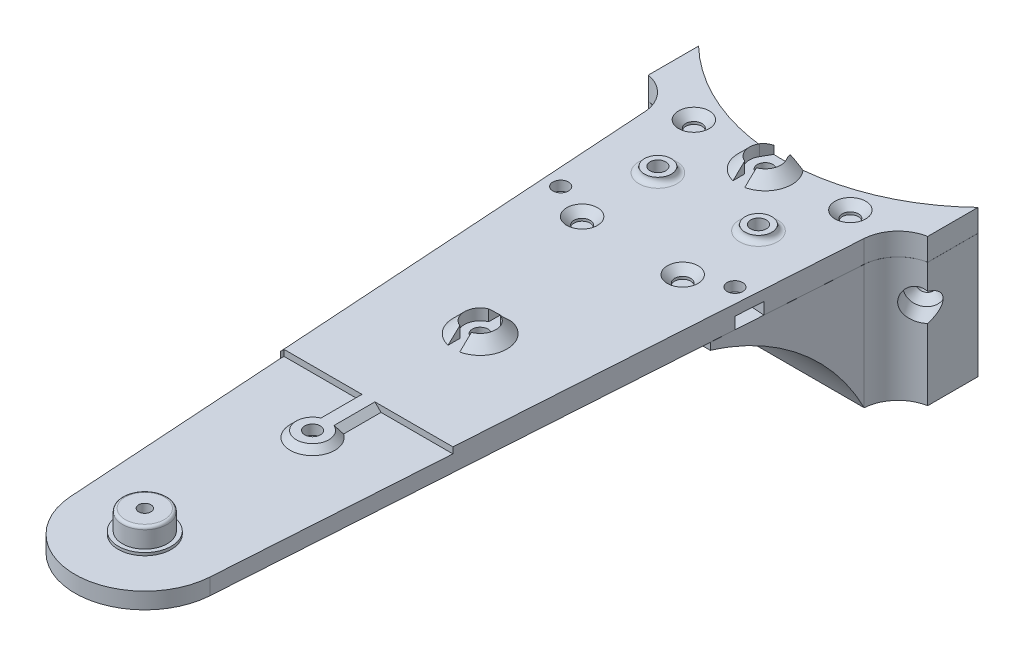
SolidWorks part; units mm, degrees
ref_plane "Front Plane" through (0, 0, 0) normal (0, 0, 1) x (1, 0, 0)
ref_plane "Top Plane" through (0, 0, 0) normal (0, 1, 0) x (1, 0, 0)
ref_plane "Right Plane" through (0, 0, 0) normal (1, 0, 0) x (0, 0, -1)
sketch "Sketch1" plane through (0, 0, 0) normal (0, 1, 0) x (1, 0, 0)
  line L0 (0, 0) -> (0, -150) construction
  line L1 (-22.2029, -1.4463) -> (-12.4736, -150.8125) construction
  line L2 (22.2029, -1.4462) -> (12.4736, -150.8125) construction
  line L3 (-12.4736, -150.8125) -> (-19.6328, -40.9037)
  line L4 (12.4736, -150.8125) -> (19.6328, -40.9037)
  line L5 (-25, -25.9037) -> (25, -25.9037) construction
  line L6 (-25, -25.9037) -> (-25, -34.9037)
  line L7 (25, -25.9037) -> (25, -34.9037)
  circle A0 centre (0, 0) radius 36 construction
  arc A1 (-12.4736, -150.8125) -> (12.4736, -150.8125) centre (0, -150) ccw
  circle A2 centre (0, 0) radius 19.5 construction
  circle A3 centre (0, 19.5) radius 2.75 construction
  circle A4 centre (0, 0) radius 22.25 construction
  arc A5 (-25, -25.9037) -> (25, -25.9037) centre (0, 0) ccw
  arc A6 (-25, -34.9037) -> (-19.6328, -40.9037) centre (-26.1442, -41.3278) cw
  arc A7 (25, -34.9037) -> (19.6328, -40.9037) centre (26.1442, -41.3278) ccw
  dimension "D1" = 72
  dimension "D3" = 25
  dimension "D4" = 39
  dimension "D5" = 5.5
  dimension "D2" = 150
  dimension "D6" = 50
  dimension "D7" = 9
  dimension "D8" = 15
extrude "Boss-Extrude1" add sketch "Sketch1" against normal blind 4
sketch "Sketch2" plane through (0, -4, 0) normal (0, -1, 0) x (1, 0, 0)
  line L0 (25, 34.9037) -> (25, 25.9037) construction
  line L1 (-25, 25.9037) -> (-25, 34.9037) construction
  line L2 (25, 34.9037) -> (25, 25.9037)
  line L3 (-25, 25.9037) -> (-25, 34.9037)
  line L4 (-19.6328, 40.9037) -> (19.6328, 40.9037)
  arc A0 (19.6328, 40.9037) -> (25, 34.9037) centre (26.1442, 41.3278) ccw construction
  arc A1 (25, 25.9037) -> (-25, 25.9037) centre (0, 0) ccw construction
  arc A2 (-25, 34.9037) -> (-19.6328, 40.9037) centre (-26.1442, 41.3278) ccw construction
  arc A3 (19.6328, 40.9037) -> (25, 34.9037) centre (26.1442, 41.3278) ccw
  arc A4 (25, 25.9037) -> (-25, 25.9037) centre (0, 0) ccw
  arc A5 (-25, 34.9037) -> (-19.6328, 40.9037) centre (-26.1442, 41.3278) ccw
extrude "Boss-Extrude2" add sketch "Sketch2" along normal offset from surface (22.2378 mm away) 26.2378 up to face at (0, 0, 65.6223)
ref_plane "Plane1" through (0, 0, 34.9037) normal (0, 0, 1) x (1, 0, 0)
fillet "Fillet2" radius 40 1 edges at (0, -4, 40.9037)
sketch "Sketch3" plane through (0, 0, 34.9037) normal (0, 0, 1) x (1, 0, 0)
  line L0 (25, 0) -> (-25, 0) construction
  line L1 (-19.6636, -22.6878) -> (19.6636, -22.6878) construction
  line L2 (-19.6636, -22.6878) -> (-19.6636, -10.6878) construction
  line L3 (-19.6636, -10.6878) -> (19.6636, -10.6878) construction
  line L4 (19.6636, -22.6878) -> (19.6636, -10.6878) construction
  line L5 (-19.6636, -22.6878) -> (19.6636, -10.6878) construction
  line L6 (-19.6636, -10.6878) -> (19.6636, -22.6878) construction
  line L7 (-19.6636, -7.9378) -> (-25, -7.9378)
  line L8 (-25, -7.9378) -> (-25, -13.4378)
  line L9 (-25, -13.4378) -> (-19.6636, -13.4378)
  line L10 (-25, -26.2378) -> (-25, 0) construction
  line L11 (0, -16.6878) -> (-25, -16.6878) construction
  line L12 (-25, -25.4378) -> (-25, -19.9378)
  line L13 (-25, -19.9378) -> (-19.6636, -19.9378)
  line L14 (-19.6636, -25.4378) -> (-25, -25.4378)
  line L15 (0, -16.6878) -> (0, 0) construction
  line L16 (19.6636, -25.4378) -> (25, -25.4378)
  line L17 (25, -19.9378) -> (19.6636, -19.9378)
  line L18 (25, -25.4378) -> (25, -19.9378)
  line L19 (25, -13.4378) -> (19.6636, -13.4378)
  line L20 (25, -7.9378) -> (25, -13.4378)
  line L21 (19.6636, -7.9378) -> (25, -7.9378)
  arc A0 (-19.6636, -13.4378) -> (-19.6636, -7.9378) centre (-19.6636, -10.6878) ccw
  arc A4 (-19.6636, -19.9378) -> (-19.6636, -25.4378) centre (-19.6636, -22.6878) cw
  arc A5 (19.6636, -19.9378) -> (19.6636, -25.4378) centre (19.6636, -22.6878) ccw
  arc A6 (19.6636, -13.4378) -> (19.6636, -7.9378) centre (19.6636, -10.6878) cw
  point P0 (0, -16.6878)
  dimension "D4" = 5.5
  dimension "D1" = 10.6878
  dimension "D2" = 12
  dimension "D3" = 39.3272
extrude "Cut-Extrude1" [suppressed] cut sketch "Sketch3" along normal through all
chamfer "Chamfer1" [suppressed] distance 2.75 angle 60
hole_wizard "CSK for M2.5 Flat Head Machine Screw1" [suppressed] positions "Sketch5" profile "Sketch6" countersink size "M2.5" standard "ANSI Metric"
sketch "Sketch5" [suppressed] plane through (0, 0, 34.9037) normal (0, 0, 1) x (1, 0, 0)
  point P0 (19.6636, -22.6878)
  point P3 (-19.6636, -22.6878)
  point P6 (-19.6636, -10.6878)
  point P9 (19.6636, -10.6878)
sketch "Sketch6" plane through (19.6636, -22.6878, 34.9037) normal (1, 0, 0) x (0, -1, 0)
  line L0 (0, 0) -> (0, 9)
  line L1 (0, 9) -> (1.4, 9)
  line L2 (1.4, 9) -> (1.4, 1.35)
  line L3 (1.4, 1.35) -> (2.75, 0)
  line L5 (2.75, 0) -> (0, 0)
  line L6 (-1.4, 1.35) -> (-2.75, 0) construction
  line L11 (0, -6.35) -> (0, 107.95) construction
  dimension "Thru Hole Dia." = 2.8
  dimension "Thru Hole Depth" = 9
  dimension "Near C'Sink Dia." = 5.5
  dimension "Near C'Sink Angle" = 90
sketch "Sketch8" plane through (0, 0, 0) normal (0, 1, 0) x (1, 0, 0)
  line L1 (1.0164, -92.5616) -> (1.0209, -117.4381) construction
  line L2 (-0.9836, -92.5619) -> (-0.9791, -117.4384) construction
  line L3 (15.1322, -109.9973) -> (15.1322, -176.6324)
  line L4 (15.1322, -176.6324) -> (-15.0896, -176.6324)
  line L5 (-15.0896, -176.6324) -> (-15.0896, -109.9973)
  line L29 (-0.9805, -109.9973) -> (-0.9791, -117.4384)
  line L30 (1.0195, -109.9973) -> (1.0209, -117.4381)
  line L31 (1.0195, -109.9973) -> (15.1322, -109.9973)
  line L72 (-15.0896, -109.9973) -> (-0.9805, -109.9973)
  arc A4 (-0.9791, -117.4384) -> (1.0209, -117.4381) centre (0.0213, -120) ccw construction
  arc A8 (-0.9791, -117.4384) -> (1.0209, -117.4381) centre (0.0213, -120) ccw
  point P0 (0.0213, -176.6324)
  dimension "D2" = 5.5
extrude "Cut-Extrude3" cut sketch "Sketch8" against normal blind 1.09
sketch "Sketch9" plane through (0, -4, 0) normal (0, -1, 0) x (1, 0, 0)
  line L0 (-17.2982, 76.7436) -> (17.2982, 76.7436)
  line L1 (17.2982, 76.7436) -> (17.9496, 66.7436)
  line L2 (17.9496, 66.7436) -> (-17.9496, 66.7436)
  line L3 (-17.9496, 66.7436) -> (-17.2982, 76.7436)
  line L4 (-17.2982, 76.7436) -> (-12.4736, 150.8125) construction
  line L5 (12.4736, 150.8125) -> (17.2982, 76.7436) construction
  dimension "D1" = 10
extrude "Cut-Extrude4" cut sketch "Sketch9" along normal through all
sketch "Sketch11" plane through (0, -4, 0) normal (0, -1, 0) x (1, 0, 0)
  circle A0 centre (0, 0) radius 161
extrude "Cut-Extrude5" cut sketch "Sketch11" along normal blind 0.01
sketch "Sketch12" plane through (0, 0, 0) normal (0, 1, 0) x (1, 0, 0)
  line L0 (-17.9496, -66.7436) -> (17.9496, -66.7436) construction
  line L1 (-17.9496, -66.7436) -> (17.9496, -66.7436) construction
  line L3 (-9, -62.7436) -> (9, -62.7436) construction
  line L4 (-9, -62.7436) -> (-14, -37.7436) construction
  line L5 (-14, -37.7436) -> (14, -37.7436) construction
  line L6 (9, -62.7436) -> (14, -37.7436) construction
  line L7 (-9, -62.7436) -> (14, -37.7436) construction
  line L8 (-14, -37.7436) -> (9, -62.7436) construction
  circle A0 centre (-14, -37.7436) radius 1.4
  circle A1 centre (14, -37.7436) radius 1.4
  circle A2 centre (-9, -62.7436) radius 1.4
  circle A3 centre (9, -62.7436) radius 1.4
  point P2 (0, -52.961)
  point P15 (0, -62.7436)
  dimension "D1" = 2.8
  dimension "D2" = 4
  dimension "D3" = 28
  dimension "D4" = 25
  dimension "D5" = 18
extrude "Cut-Extrude6" cut sketch "Sketch12" against normal blind 8.25
ref_plane "Plane2" through (0, -5.2702, 0) normal (0, 1, 0) x (1, 0, 0)
sketch "Sketch13" plane through (0, -5.2702, 0) normal (0, 1, 0) x (1, 0, 0)
  line L0 (-11.45, -64.1582) -> (-11.45, -66.7436)
  line L5 (-9, -65.5727) -> (-6.55, -64.1582) construction
  line L6 (-6.55, -64.1582) -> (-6.55, -61.3291)
  line L17 (-6.55, -61.3291) -> (-9, -59.9146)
  line L18 (-9, -59.9146) -> (-11.45, -61.3291)
  line L19 (-11.45, -61.3291) -> (-11.45, -64.1582)
  line L20 (-11.45, -64.1582) -> (-9, -65.5727) construction
  line L21 (-17.9496, -66.7436) -> (17.9496, -66.7436) construction
  line L22 (-11.45, -66.7436) -> (-6.55, -66.7436)
  line L23 (-6.55, -66.7436) -> (-6.55, -64.1582)
  line L24 (0, 0) -> (0, -162.5) construction
  line L25 (11.45, -66.7436) -> (6.55, -66.7436)
  line L26 (11.45, -64.1582) -> (11.45, -66.7436)
  line L27 (11.45, -61.3291) -> (11.45, -64.1582)
  line L28 (9, -59.9146) -> (11.45, -61.3291)
  line L29 (6.55, -61.3291) -> (9, -59.9146)
  line L30 (6.55, -64.1582) -> (6.55, -61.3291)
  line L31 (6.55, -66.7436) -> (6.55, -64.1582)
  circle A1 centre (-9, -62.7436) radius 2.45 construction
  arc A2 (-12.4736, -150.8125) -> (12.4736, -150.8125) centre (0, -150) ccw construction
  dimension "D1" = 4.9
extrude "Cut-Extrude7" cut sketch "Sketch13" against normal blind 8.5
sketch "Sketch14" plane through (0, -8.25, 0) normal (0, 1, 0) x (1, 0, 0)
  line L0 (0, 0) -> (0, -36) construction
  line L1 (-14, -37.7436) -> (0, 0) construction
  line L6 (-15.8051, -35.5654) -> (-14.7878, -32.8226)
  line L7 (-13.0162, -35.0912) -> (-15.8051, -35.5654) construction
  line L17 (-15.8051, -35.5654) -> (-16.789, -38.2178)
  line L18 (-16.789, -38.2178) -> (-14.9838, -40.3961)
  line L19 (-14.9838, -40.3961) -> (-12.1949, -39.9219)
  line L20 (-12.1949, -39.9219) -> (-11.211, -37.2695)
  line L21 (-11.211, -37.2695) -> (-13.0162, -35.0912) construction
  line L22 (-14.7878, -32.8226) -> (-10.1936, -34.5267)
  line L23 (-10.1936, -34.5267) -> (-11.211, -37.2695)
  line L24 (14.7878, -32.8226) -> (10.1936, -34.5267)
  line L25 (15.8051, -35.5654) -> (14.7878, -32.8226)
  line L26 (15.8051, -35.5654) -> (16.789, -38.2178)
  line L27 (16.789, -38.2178) -> (14.9838, -40.3961)
  line L28 (14.9838, -40.3961) -> (12.1949, -39.9219)
  line L29 (12.1949, -39.9219) -> (11.211, -37.2695)
  line L30 (10.1936, -34.5267) -> (11.211, -37.2695)
  arc A0 (-25, -25.9037) -> (25, -25.9037) centre (0, 0) ccw construction
  circle A1 centre (-14, -37.7436) radius 2.45 construction
  dimension "D1" = 4.9
extrude "Cut-Extrude8" cut sketch "Sketch14" along normal blind 2.5
hole_wizard "CSK for M2.5 Flat Head Machine Screw3" positions "Sketch15" profile "Sketch16" countersink size "M2.5" standard "ANSI Metric"
sketch "Sketch15" plane through (0, 0, 0) normal (0, 1, 0) x (1, 0, 0)
  point P0 (-14, -37.7436)
  point P3 (14, -37.7436)
  point P6 (9, -62.7436)
  point P9 (-9, -62.7436)
sketch "Sketch16" plane through (-14, 0, 37.7436) normal (1, 0, 0) x (0, 0, 1)
  line L0 (0, 0) -> (0, 7.8712)
  line L1 (0, 7.8712) -> (1.45, 7)
  line L2 (1.45, 7) -> (1.45, 1.3)
  line L3 (1.45, 1.3) -> (2.75, 0)
  line L5 (2.75, 0) -> (0, 0)
  line L6 (-1.45, 1.3) -> (-2.75, 0) construction
  line L10 (0, 7.8712) -> (-1.45, 7) construction
  line L11 (0, -6.35) -> (0, 107.95) construction
  dimension "Hole Dia." = 2.9
  dimension "Hole Depth" = 7
  dimension "Near C'Sink Dia." = 5.5
  dimension "Near C'Sink Angle" = 90
  dimension "Drill Angle" = 118
sketch "Sketch18" plane through (0, -4, 0) normal (0, -1, 0) x (1, 0, 0)
  circle A1 centre (0.0071, 39) radius 2.75
  circle A2 centre (0.0071, 39) radius 2.75 construction
  circle A3 centre (0.016, 90) radius 2.8 construction
  arc A5 (1.0209, 117.4381) -> (-0.9791, 117.4384) centre (0.0213, 120) ccw construction
  circle A9 centre (-15.5725, 60.0029) radius 1.4
  circle A11 centre (-15.5725, 60.0029) radius 2.75
  circle A12 centre (-15.5725, 60.0029) radius 2.75 construction
  circle A13 centre (15.5944, 59.9971) radius 1.4
  circle A15 centre (0.0071, 39) radius 1.4
  circle A17 centre (15.5944, 59.9971) radius 2.75
  circle A18 centre (15.5944, 59.9971) radius 2.75 construction
  arc A19 (1.0209, 117.4381) -> (-0.9791, 117.4384) centre (0.0213, 120) ccw construction
  circle A20 centre (0.0213, 120) radius 1.4
  circle A21 centre (0.016, 90) radius 2.8 construction
  circle A22 centre (0.016, 90) radius 1.4
  dimension "D2" = 2.8
  dimension "D1" = 0
  dimension "D6" = 0
  dimension "D9" = 0
extrude "Cut-Extrude9" cut sketch "Sketch18" against normal through all
sketch "Sketch19" plane through (0, -4, 0) normal (0, -1, 0) x (1, 0, 0)
  line L1 (1.4358, 122.45) -> (-1.3932, 122.45)
  line L2 (-1.3932, 122.45) -> (-2.8077, 120)
  line L3 (-2.8077, 120) -> (-1.3932, 117.55)
  line L4 (-1.3932, 117.55) -> (1.4358, 117.55)
  line L5 (1.4358, 117.55) -> (2.8503, 120)
  line L6 (2.8503, 120) -> (1.4358, 122.45)
  line L7 (1.4305, 92.45) -> (-1.3985, 92.45)
  line L8 (-1.3985, 92.45) -> (-2.813, 90)
  line L9 (-2.813, 90) -> (-1.3985, 87.55)
  line L10 (-1.3985, 87.55) -> (1.4305, 87.55)
  line L11 (1.4305, 87.55) -> (2.845, 90)
  line L12 (2.845, 90) -> (1.4305, 92.45)
  line L13 (-12.7494, 59.819) -> (-14.0017, 62.3557)
  line L14 (-14.0017, 62.3557) -> (-16.8247, 62.5396)
  line L15 (-16.8247, 62.5396) -> (-18.3955, 60.1867) construction
  line L16 (-18.3955, 60.1867) -> (-17.1432, 57.65) construction
  line L17 (-17.1432, 57.65) -> (-14.3202, 57.4661)
  line L18 (-14.3202, 57.4661) -> (-12.7494, 59.819)
  line L19 (2.4536, 37.5793) -> (2.4607, 40.4083)
  line L20 (2.4607, 40.4083) -> (0.0143, 41.829)
  line L21 (0.0143, 41.829) -> (-2.4393, 40.4207)
  line L22 (-2.4393, 40.4207) -> (-2.4464, 37.5917)
  line L23 (-2.4464, 37.5917) -> (0, 36.171) construction
  line L24 (0, 36.171) -> (2.4536, 37.5793) construction
  line L25 (0, 0) -> (0, 162.5) construction
  line L26 (-18.3955, 60.1867) -> (-15.5725, 60.0029) construction
  line L27 (-19.6328, 40.9037) -> (-12.4736, 150.8125) construction
  line L28 (-16.8247, 62.5396) -> (-18.2176, 62.6303)
  line L29 (-18.2176, 62.6303) -> (-18.5361, 57.7407)
  line L30 (-18.5361, 57.7407) -> (-17.1432, 57.65)
  line L31 (18.2176, 62.6303) -> (18.5361, 57.7407)
  line L32 (16.8247, 62.5396) -> (18.2176, 62.6303)
  line L33 (14.0017, 62.3557) -> (16.8247, 62.5396)
  line L34 (12.7494, 59.819) -> (14.0017, 62.3557)
  line L35 (14.3202, 57.4661) -> (12.7494, 59.819)
  line L36 (17.1432, 57.65) -> (14.3202, 57.4661)
  line L37 (18.5361, 57.7407) -> (17.1432, 57.65)
  line L38 (-2.4464, 37.5917) -> (-2.4464, 35.9168)
  line L39 (-2.4464, 35.9168) -> (2.4536, 35.9163)
  line L40 (2.4536, 35.9163) -> (2.4536, 37.5793)
  circle A0 centre (0.0213, 120) radius 2.45 construction
  circle A1 centre (0.016, 90) radius 2.45 construction
  circle A2 centre (-15.5725, 60.0029) radius 2.45 construction
  circle A3 centre (0.0071, 39) radius 2.45 construction
  arc A4 (12.4736, 150.8125) -> (-12.4736, 150.8125) centre (0, 150) ccw construction
  arc A5 (25, 25.9037) -> (-25, 25.9037) centre (0, 0) ccw construction
  circle A6 centre (0.0213, 120) radius 1.4 construction
  circle A7 centre (0.016, 90) radius 1.4 construction
  dimension "D1" = 4.9
extrude "Cut-Extrude10" cut sketch "Sketch19" against normal blind 2.1
sketch "Sketch20" plane through (0, -1.09, 0) normal (0, 1, 0) x (1, 0, 0)
  circle A0 centre (0, -150) radius 4.75
  dimension "D1" = 9.5
extrude "Boss-Extrude3" add sketch "Sketch20" along normal blind 0.5
sketch "Sketch21" plane through (0, -0.59, 0) normal (0, 1, 0) x (1, 0, 0)
  circle A0 centre (0, -150) radius 4
  dimension "D1" = 8
extrude "Boss-Extrude4" add sketch "Sketch21" along normal blind 3.5
fillet "Fillet4" radius 0.5 1 edges at (0, 2.91, 154)
sketch "Sketch22" plane through (0, 0, 0) normal (0, 1, 0) x (1, 0, 0)
  line L0 (0, 0) -> (0, -150) construction
  circle A0 centre (0, 0) radius 50 construction
  arc A1 (-25, -25.9037) -> (25, -25.9037) centre (0, 0) ccw construction
  circle A2 centre (9, -49.1833) radius 1.4
  circle A3 centre (9, -49.1833) radius 3.5 construction
  circle A4 centre (-9, -49.1833) radius 1.4
  dimension "D1" = 100
  dimension "D2" = 2.8
  dimension "D4" = 7
  dimension "D3" = 9
extrude "Cut-Extrude12" cut sketch "Sketch22" against normal through all contours A2 | A4
sketch "Sketch24" plane through (0, 2.91, 0) normal (0, -1, 0) x (1, 0, 0)
  circle A0 centre (0, 150) radius 1.1
  dimension "D1" = 2.2
extrude "Cut-Extrude13" cut sketch "Sketch24" along normal through all
ref_plane "Plane3" through (0, 0, 36) normal (0, 0, -1) x (-1, 0, 0)
sketch "Sketch25" plane through (0, 0, 36) normal (0, 0, -1) x (-1, 0, 0)
  line L0 (-25, -26.2378) -> (25, -26.2378) construction
  line L1 (0, 0) -> (0, -26.2378) construction
  line L2 (-14.13, -16) -> (-10.13, -16)
  line L3 (-14.13, -16) -> (-14.13, -19)
  line L4 (-14.13, -19) -> (-10.13, -19)
  line L5 (-10.13, -16) -> (-10.13, -19)
  line L6 (10.13, -16) -> (10.13, -19)
  line L7 (14.13, -19) -> (10.13, -19)
  line L8 (14.13, -16) -> (14.13, -19)
  line L9 (14.13, -16) -> (10.13, -16)
  point P0 (0, -25.021)
  dimension "D1" = 16
  dimension "D2" = 20.26
  dimension "D3" = 4
  dimension "D4" = 3
extrude "Boss-Extrude6" add sketch "Sketch25" along normal blind 3
chamfer "Chamfer2" distance 1.8 angle 45 2 edges at (-12.1512, -19, 33.8873) (12.1512, -19, 33.8873)
chamfer "Chamfer3" [suppressed] distance 2 angle 45
chamfer "Chamfer4" distance 1.25 angle 45 3 edges at (0.0218, -1.09, 122.75) (-0.9798, -1.09, 113.7179) (1.0202, -1.09, 113.7177)
sketch "Sketch26" [suppressed] plane through (0, -4, 0) normal (0, -1, 0) x (1, 0, 0)
  line L0 (-18.2159, 62.6553) -> (-12.4736, 150.8125) construction
  line L1 (12.4736, 150.8125) -> (18.2159, 62.6553) construction
  line L2 (-18.2159, 62.6553) -> (-17.9496, 66.7436)
  line L3 (17.9496, 66.7436) -> (18.2159, 62.6553)
  line L4 (-17.9496, 66.7436) -> (17.9496, 66.7436) construction
  line L5 (-17.9496, 66.7436) -> (-15.9454, 66.7436)
  line L6 (18.2159, 62.6553) -> (16.2202, 62.5253)
  line L7 (16.2202, 62.5253) -> (15.9454, 66.7436)
  line L8 (-18.2159, 62.6553) -> (-16.2202, 62.5253)
  line L9 (-10.4778, 150.6825) -> (-16.2202, 62.5253) construction
  line L10 (-16.2202, 62.5253) -> (-15.9454, 66.7436)
  line L11 (15.9454, 66.7436) -> (17.9496, 66.7436)
extrude "Boss-Extrude7" [suppressed] add sketch "Sketch26" against normal up to surface (4 mm away)
sketch "Sketch29" plane through (0, 0, 0) normal (0, 1, 0) x (1, 0, 0)
  line L0 (-19.0027, -30.5761) -> (-10.8155, -156.2669) construction
  line L1 (-19.6328, -40.9037) -> (-15.0896, -110.6516) construction
  line L2 (-17.2328, -57.7482) -> (-17.3757, -55.5544) construction
  line L3 (-16.9263, -62.4538) -> (-16.7834, -64.6476) construction
  line L4 (0, 0) -> (0, -162.5) construction
  line L5 (16.9263, -62.4538) -> (16.7834, -64.6476) construction
  line L6 (17.2328, -57.7482) -> (17.3757, -55.5544) construction
  line L7 (-2.4177, -37.6) -> (-1.4765, -35.9697)
  line L8 (2.432, -37.6) -> (1.4919, -35.9691)
  line L9 (-1.05, -41.5928) -> (-1.05, -43.6821)
  line L10 (-1.05, -85.3199) -> (-1.05, -87.4109)
  line L11 (1.05, -85.3127) -> (1.05, -87.3979)
  line L12 (1.05, -41.5928) -> (1.05, -43.6853)
  line L13 (-1.05, -92.5891) -> (-1.05, -94.6801)
  line L14 (1.05, -92.6021) -> (1.05, -94.6873)
  arc A0 (-1.05, -87.4109) -> (-1.05, -92.5891) centre (0.016, -90) ccw
  arc A1 (-1.05, -85.3199) -> (-1.05, -94.6801) centre (0.016, -90) ccw
  arc A2 (-16.9263, -62.4538) -> (-17.2328, -57.7482) centre (-15.5725, -60.0029) ccw construction
  arc A4 (-25, -25.9037) -> (25, -25.9037) centre (0, 0) ccw construction
  arc A5 (-12.4736, -150.8125) -> (12.4736, -150.8125) centre (0, -150) ccw construction
  arc A6 (-10.8209, -60.6829) -> (-17.3757, -55.5544) centre (-15.5725, -60.0029) ccw construction
  circle A7 centre (-9, -62.7436) radius 2.75 construction
  arc A8 (-10.8209, -60.6829) -> (-11.7455, -62.9002) centre (-9, -62.7436) ccw construction
  arc A9 (-2.4177, -37.6) -> (-1.05, -41.5928) centre (0.0071, -39) ccw
  arc A10 (-16.7834, -64.6476) -> (-11.7455, -62.9002) centre (-15.5725, -60.0029) ccw construction
  arc A11 (16.7834, -64.6476) -> (11.7455, -62.9002) centre (15.5725, -60.0029) cw construction
  arc A12 (10.8209, -60.6829) -> (11.7455, -62.9002) centre (9, -62.7436) cw construction
  arc A13 (10.8209, -60.6829) -> (17.3757, -55.5544) centre (15.5725, -60.0029) cw construction
  arc A14 (16.9263, -62.4538) -> (17.2328, -57.7482) centre (15.5725, -60.0029) cw construction
  arc A15 (-3.5889, -35.8207) -> (-1.05, -43.6821) centre (0.0071, -39) ccw
  arc A16 (-25, -25.9037) -> (-19.0027, -30.5761) centre (0, 0) ccw
  arc A17 (-3.5889, -35.8207) -> (-1.4765, -35.9697) centre (0, 0) ccw
  arc A18 (1.4919, -35.9691) -> (3.6021, -35.8193) centre (0, 0) ccw
  arc A19 (1.05, -43.6853) -> (3.6021, -35.8193) centre (0.0071, -39) ccw
  arc A20 (1.05, -41.5985) -> (2.432, -37.6) centre (0.0071, -39) ccw
  arc A21 (1.05, -92.6021) -> (1.05, -87.3979) centre (0.016, -90) ccw
  arc A22 (1.05, -94.6873) -> (1.05, -85.3127) centre (0.016, -90) ccw
  arc M17 (25, -25.9037) -> (-25, -25.9037) centre (0, 0) cw
  dimension "D1" = 5.6
  dimension "D2" = 2
  dimension "D3" = 5.6
  dimension "D5" = 2
  dimension "D6" = 5.6
  dimension "D7" = 2
  dimension "D4" = 1.3
  dimension "D8" = 30
  dimension "D9" = 2.1
extrude "Boss-Extrude8" add sketch "Sketch29" along normal blind 2 contours A15 L8 A9 L7 M17 | A1 A0 | A21 L11 A22 L14
chamfer "Chamfer5" distance 2 angle 45 4 edges at (-4.784, 2, 90) (4.5729, 2, 40.4813) (-4.5606, 2, 40.4752) (4.816, 2, 90)
ref_plane "Plane4" [suppressed] through (0, 0, 0) normal (-1, 0, 0) x (0, 0, 1)
sketch "Sketch30" plane through (0, 0, 0) normal (0, 1, 0) x (1, 0, 0)
  line L0 (0, 0) -> (0, -64.331) construction
  line L1 (0, 0) -> (-20.1309, -29.8454) construction
  arc A0 (-25, -25.9037) -> (-3.5889, -35.8207) centre (0, 0) ccw construction
  dimension "D1" = 34
ref_plane "Plane5" through (-20.1309, 0, 29.8454) normal (0.5592, 0, -0.829) x (-0.829, 0, -0.5592)
ref_plane "Plane6" through (-21.8085, 0, 32.3325) normal (0.5592, 0, -0.829) x (-0.829, 0, -0.5592)
sketch "Sketch31" plane through (-21.8085, 0, 32.3325) normal (0.5592, 0, -0.829) x (-0.829, 0, -0.5592)
  line L0 (6.2408, 0) -> (-17.0553, 0) construction
  circle A0 centre (0, -11) radius 2.75
  dimension "D1" = 5.5
  dimension "D2" = 11
extrude "Cut-Extrude14" cut sketch "Sketch31" against normal blind 10
hole_wizard "CSK for M2.5 Flat Head Machine Screw2" positions "Sketch34" profile "Sketch33" countersink size "M2.5" standard "ANSI Metric" end condition through all
sketch "Sketch34" plane through (-21.8085, 0, 32.3325) normal (-0.5592, 0, 0.829) x (0.829, 0, 0.5592)
  point P0 (0, -11)
sketch "Sketch33" plane through (-21.8085, -11, 32.3325) normal (0, 1, 0) x (0.829, 0, 0.5592)
  line L0 (0, 0) -> (0, 31.6027)
  line L1 (0, 31.6027) -> (1.45, 31.6027)
  line L2 (1.45, 31.6027) -> (1.45, 1.3)
  line L3 (1.45, 1.3) -> (2.75, 0)
  line L5 (2.75, 0) -> (0, 0)
  line L6 (-1.45, 1.3) -> (-2.75, 0) construction
  line L11 (0, -6.35) -> (0, 107.95) construction
  dimension "Thru Hole Dia." = 2.9
  dimension "Thru Hole Depth" = 31.6027
  dimension "Near C'Sink Dia." = 5.5
  dimension "Near C'Sink Angle" = 90
mirror "Mirror1" about plane through (0, 0, 0) normal (1, 0, 0) of "Cut-Extrude14", "CSK for M2.5 Flat Head Machine Screw2"
sketch "Sketch35" plane through (0, -4, 0) normal (0, -1, 0) x (1, 0, 0)
  line L1 (2.3094, 150) -> (1.1547, 152)
  line L2 (1.1547, 152) -> (-1.1547, 152)
  line L3 (-1.1547, 152) -> (-2.3094, 150)
  line L4 (-2.3094, 150) -> (-1.1547, 148)
  line L5 (-1.1547, 148) -> (1.1547, 148)
  line L6 (1.1547, 148) -> (2.3094, 150)
  circle A0 centre (0, 150) radius 2 construction
  dimension "D1" = 4
extrude "Cut-Extrude15" cut sketch "Sketch35" against normal blind 2 contours L4 L5 L6 L1 L2 L3
sketch "Sketch37" plane through (0, -1.9, 0) normal (0, -1, 0) x (1, 0, 0)
  line L0 (-18.2176, 62.6303) -> (-18.5361, 57.7407)
  line L1 (18.2176, 62.6303) -> (18.5361, 57.7407)
  line L2 (-2.4464, 35.9168) -> (2.4536, 35.9163)
  line L20 (19.6328, 40.9037) -> (18.5361, 57.7407)
  line L21 (18.5361, 57.7407) -> (14.3202, 57.4661)
  line L22 (14.3202, 57.4661) -> (12.7494, 59.819)
  line L23 (12.7494, 59.819) -> (14.0017, 62.3557)
  line L24 (14.0017, 62.3557) -> (18.2176, 62.6303)
  line L25 (18.2176, 62.6303) -> (12.4736, 150.8125)
  line L26 (-12.4736, 150.8125) -> (-18.2176, 62.6303)
  line L27 (-18.2176, 62.6303) -> (-14.0017, 62.3557)
  line L28 (-14.0017, 62.3557) -> (-12.7494, 59.819)
  line L29 (-12.7494, 59.819) -> (-14.3202, 57.4661)
  line L30 (-14.3202, 57.4661) -> (-18.5361, 57.7407)
  line L31 (-18.5361, 57.7407) -> (-19.6328, 40.9037)
  line L32 (-25, 34.9037) -> (-25, 25.9037)
  line L33 (-2.4464, 35.9168) -> (-2.4464, 37.5917)
  line L34 (-2.4464, 37.5917) -> (-2.4393, 40.4207)
  line L35 (-2.4393, 40.4207) -> (0.0143, 41.829)
  line L36 (0.0143, 41.829) -> (2.4607, 40.4083)
  line L37 (2.4607, 40.4083) -> (2.4536, 37.5793)
  line L38 (2.4536, 37.5793) -> (2.4536, 35.9163)
  line L39 (25, 25.9037) -> (25, 34.9037)
  line L40 (19.6328, 40.9037) -> (18.5361, 57.7407)
  line L45 (18.2176, 62.6303) -> (12.4736, 150.8125)
  line L46 (-12.4736, 150.8125) -> (-18.2176, 62.6303)
  line L51 (-18.5361, 57.7407) -> (-19.6328, 40.9037)
  line L52 (-25, 34.9037) -> (-25, 25.9037)
  line L59 (25, 25.9037) -> (25, 34.9037)
  circle A0 centre (0, 150) radius 1.1
  circle A1 centre (0, 150) radius 1.1 construction
  arc A5 (12.4736, 150.8125) -> (-12.4736, 150.8125) centre (0, 150) ccw
  arc A6 (-25, 34.9037) -> (-19.6328, 40.9037) centre (-26.1442, 41.3278) ccw
  arc A7 (-2.4464, 35.9168) -> (-25, 25.9037) centre (0, 0) ccw
  arc A8 (25, 25.9037) -> (2.4536, 35.9163) centre (0, 0) ccw
  arc A9 (19.6328, 40.9037) -> (25, 34.9037) centre (26.1442, 41.3278) ccw
  arc A10 (12.4736, 150.8125) -> (-12.4736, 150.8125) centre (0, 150) ccw
  arc A11 (-25, 34.9037) -> (-19.6328, 40.9037) centre (-26.1442, 41.3278) ccw
  arc A12 (-2.4464, 35.9168) -> (-25, 25.9037) centre (0, 0) ccw
  arc A13 (25, 25.9037) -> (2.4536, 35.9163) centre (0, 0) ccw
  arc A14 (19.6328, 40.9037) -> (25, 34.9037) centre (26.1442, 41.3278) ccw
  dimension "D1" = 0
extrude "sacrificial layer" add sketch "Sketch37" against normal blind 0.15
sketch "Sketch38" plane through (0, -2, 0) normal (0, -1, 0) x (1, 0, 0)
  circle A0 centre (0, 150) radius 2.3094
extrude "Boss-Extrude9" add sketch "Sketch38" against normal blind 0.15
sketch "Sketch39" plane through (0, 0, 0) normal (0, 1, 0) x (1, 0, 0)
  line L0 (0, 0) -> (0, -73.9232) construction
  circle A0 centre (9, -49.1833) radius 2.4
  circle A1 centre (9, -49.1833) radius 1.4
  circle A2 centre (9, -49.1833) radius 1.4 construction
  circle A3 centre (-9, -49.1833) radius 1.4
  circle A4 centre (-9, -49.1833) radius 2.4
  dimension "D1" = 4.8
extrude "Boss-Extrude10" add sketch "Sketch39" along normal blind 1
fillet "Fillet5" radius 1 2 edges at (9, 0, 51.5833) (-9, 0, 46.7833)
